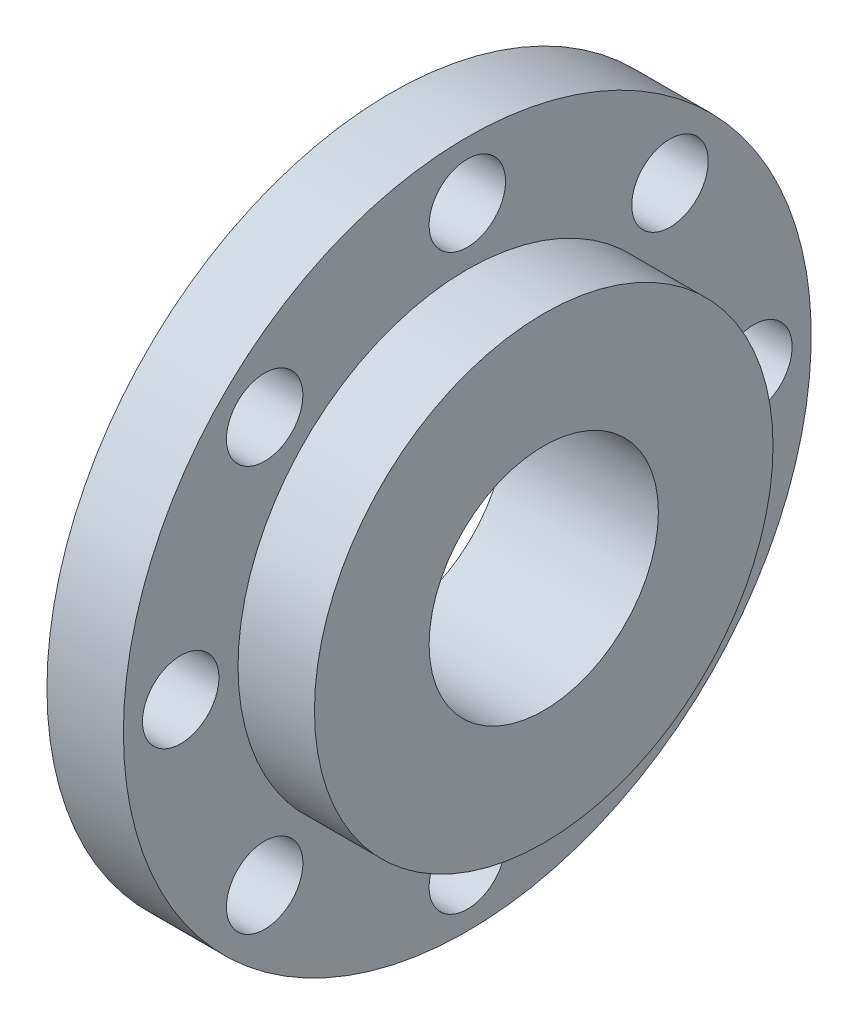
SolidWorks part; units mm, degrees
ref_plane "Front Plane" through (0, 0, 0) normal (0, 0, 1) x (1, 0, 0)
ref_plane "Top Plane" through (0, 0, 0) normal (0, 1, 0) x (1, 0, 0)
ref_plane "Right Plane" through (0, 0, 0) normal (1, 0, 0) x (0, 0, -1)
sketch "Sketch2" plane through (0, 0, 0) normal (0, 0, 1) x (1, 0, 0)
  line L0 (0, 0) -> (38.8393, 0) construction
  line L1 (0, 15) -> (20, 15)
  line L2 (20, 15) -> (20, 30)
  line L3 (10, 30) -> (10, 45)
  line L4 (10, 45) -> (0, 45)
  line L5 (0, 45) -> (0, 15)
  line L6 (20, 30) -> (10, 30)
  point P9 (0, 0)
  point P10 (20.9821, 28.75)
  point P11 (11.7208, 35.4989)
  point P12 (0, 0)
  point P13 (0, 0)
  dimension "D1" = 90
  dimension "D2" = 10
  dimension "D3" = 30
  dimension "D4" = 10
  dimension "D5" = 60
revolve "Revolve1" add sketch "Sketch2" angle 360 about L0
sketch "Sketch3" plane through (0, 0, 0) normal (-1, 0, 0) x (0, 0, 1)
  circle A0 centre (0, 0) radius 37.5 construction
  circle A1 centre (0, 37.5) radius 5
  circle A2 centre (26.5165, 26.5165) radius 5
  circle A3 centre (37.5, 0) radius 5
  circle A4 centre (26.5165, -26.5165) radius 5
  circle A5 centre (0, -37.5) radius 5
  circle A6 centre (-26.5165, -26.5165) radius 5
  circle A7 centre (-37.5, 0) radius 5
  circle A8 centre (-26.5165, 26.5165) radius 5
  point P6 (-74.3126, -5.0379)
  point P7 (0, 0)
  point P21 (0, 0)
  point P22 (0, 0)
  dimension "D1" = 75
  dimension "D2" = 10
  dimension "D3" = 8
extrude "Cut-Extrude1" cut sketch "Sketch3" against normal through all
